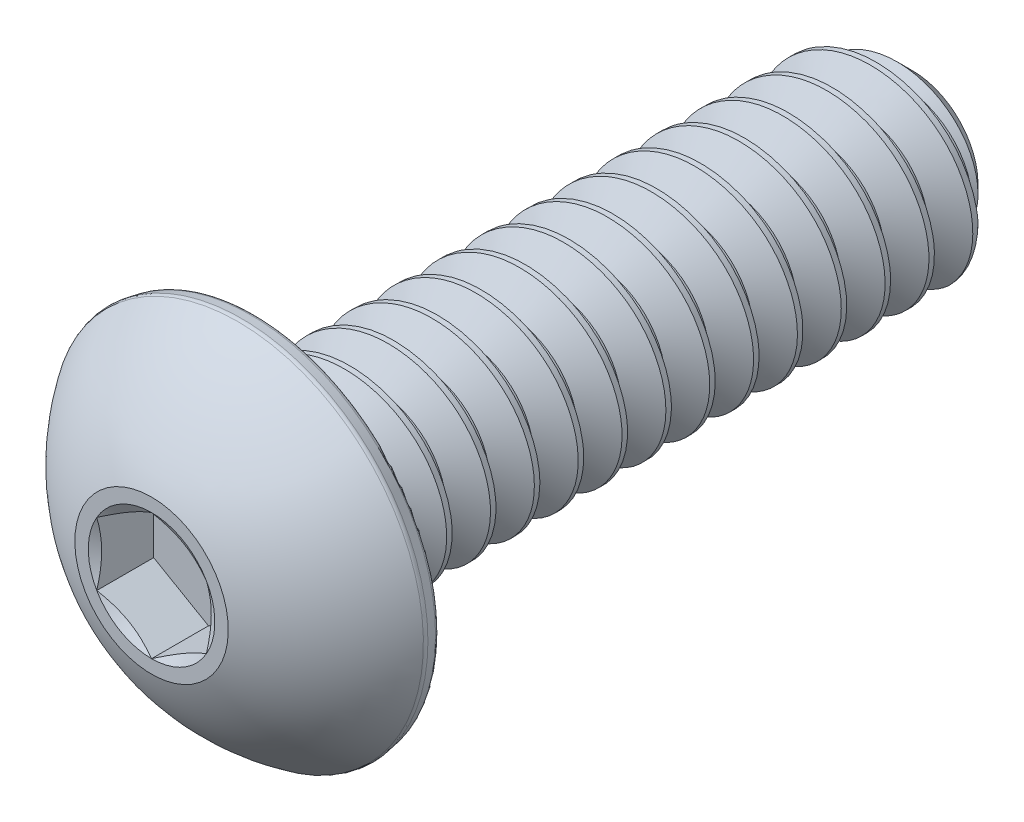
SolidWorks part; units mm, degrees
material "Stainless Steel (ferritic)"
ref_plane "Front Plane" through (0, 0, 0) normal (0, 0, 1) x (1, 0, 0)
ref_plane "Top Plane" through (0, 0, 0) normal (0, 1, 0) x (1, 0, 0)
ref_plane "Right Plane" through (0, 0, 0) normal (1, 0, 0) x (0, 0, -1)
sketch "Sketch1" plane through (0, 0, 0) normal (1, 0, 0) x (0, 0, -1)
  line L0 (-5.5118, 0) -> (5.5118, 0) construction
  line L1 (-5.5118, 0) -> (-5.5118, 2.7051)
  line L2 (-5.5118, 2.7051) -> (-4.0132, 2.7051)
  line L3 (-4.0132, 2.7051) -> (-4.0132, 1.4224)
  line L4 (-4.0132, 1.4224) -> (5.5118, 1.4224)
  line L5 (5.5118, 1.4224) -> (5.5118, 0)
  point P2 (0, 0)
  point P4 (4.8768, 0)
  point P9 (4.5593, 1.4224)
  point P10 (4.5593, -1.4224)
  point P11 (5.5118, -1.4224)
  point P15 (-4.6876, 0)
  dimension "Head Height" = 1.4986
  dimension "Head Diameter" = 5.4102
  dimension "Length" = 9.525
  dimension "Screw Size Decimal Equivalent" = 2.8448
  dimension "Thread Pitch" = 0.635
  dimension "D1" = 0.9525
  dimension "D2" = 0.8242
sketch "Sketch2" plane through (0, 0, 0) normal (0, 0, 1) x (1, 0, 0)
  line L0 (0, 1.4224) -> (0, 0) construction
  line L1 (0, 0.9165) -> (-0.7937, 0.4583)
  line L2 (-0.7937, 0.4583) -> (-0.7937, -0.4583)
  line L3 (-0.7937, -0.4583) -> (0, -0.9165)
  line L4 (0, -0.9165) -> (0.7937, -0.4583)
  line L5 (0.7937, -0.4583) -> (0.7937, 0.4583)
  line L6 (0.7937, 0.4583) -> (0, 0.9165)
  circle A0 centre (0, 0) radius 0.7937 construction
  circle A1 centre (0, 0) radius 1.1113
  point P10 (0, 1.1113)
  dimension "D1" = 2.2225
  dimension "Drive Size" = 1.5875
sketch "Sketch3" plane through (0, 0, 0) normal (1, 0, 0) x (0, 0, -1)
  line L0 (-5.5118, 0) -> (-5.5118, 1.1113)
  line L1 (-5.5118, 0) -> (-5.5118, 2.7051) construction
  line L2 (-5.5118, 2.7051) -> (-4.0132, 2.7051) construction
  line L3 (-4.238, 2.7051) -> (-4.0132, 2.6655)
  line L4 (-4.0132, 2.7051) -> (-4.0132, 1.4224) construction
  line L5 (-4.0132, 2.6655) -> (-4.0132, 1.4224)
  line L6 (-5.5118, 0) -> (5.5118, 0) construction
  line L7 (-5.5118, 0) -> (5.5118, 0)
  line L8 (5.5118, 0) -> (5.5118, 0.9462)
  line L9 (5.5118, 1.4224) -> (5.5118, 0) construction
  line L10 (5.5118, 0.9462) -> (5.0355, 1.4224)
  line L11 (-4.0132, 1.4224) -> (5.5118, 1.4224) construction
  line L12 (5.0355, 1.4224) -> (-4.0132, 1.4224)
  arc A0 (-5.5118, 1.1113) -> (-4.238, 2.7051) centre (-2.4873, 0) cw
  dimension "D1" = 0.2248
  dimension "D2" = 10
  dimension "D3" = 45
  dimension "D4" = 0.4763
revolve "Revolve1" add sketch "Sketch3" angle 360 about L7
sketch "Sketch4" plane through (0, 0, 5.5118) normal (0, 0, 1) x (1, 0, 0)
  line L0 (-0.7937, -0.4583) -> (0, -0.9165) construction
  line L1 (-0.7937, 0.4583) -> (-0.7937, -0.4583) construction
  line L2 (0, 0.9165) -> (-0.7937, 0.4583) construction
  line L3 (0.7937, 0.4583) -> (0, 0.9165) construction
  line L4 (0.7937, -0.4583) -> (0.7937, 0.4583) construction
  line L5 (0, -0.9165) -> (0.7937, -0.4583) construction
  line L6 (-0.7937, -0.4583) -> (0, -0.9165)
  line L7 (-0.7937, 0.4583) -> (-0.7937, -0.4583)
  line L8 (0, 0.9165) -> (-0.7937, 0.4583)
  line L9 (0.7937, 0.4583) -> (0, 0.9165)
  line L10 (0.7937, -0.4583) -> (0.7937, 0.4583)
  line L11 (0, -0.9165) -> (0.7937, -0.4583)
extrude "Cut-Extrude1" cut sketch "Sketch4" against normal up to vertex (0.8242 mm away) up to point (0, 0, 4.6876)
sketch "Sketch5" plane through (0, 0, 5.5118) normal (0, 0, 1) x (1, 0, 0)
  circle A0 centre (0, 0) radius 0.9165
extrude "Cut-Extrude2" cut sketch "Sketch5" against normal up to vertex (0.8242 mm away) draft 60 up to point (0, 0, 4.6876)
fillet "Fillet1" radius 0.0749 2 edges at (2.7051, 0, 4.238) (2.6655, 0, 4.0132)
split "Split1" bodies to split 106 resulting bodies 107 108 split by face at (2.6026, 0, 4.0132)
sketch "Sketch6" plane through (0, 0, -5.5118) normal (0, 0, -1) x (-1, 0, 0)
  circle A0 centre (0, 0) radius 1.4224 construction
  circle A1 centre (0, 0) radius 1.4224
curve "Helix/Spiral1" pitch 0.635 height 10.16 radius 1.4224 centre (0, 0, -5.5118) axis (0, 0, 1) start towards (0, 1, 0)
sketch "Sketch7" plane through (0, 0, 0) normal (1, 0, 0) x (0, 0, -1)
  line L0 (5.4721, 1.4911) -> (5.7896, 0.9412) construction
  line L1 (5.7896, 0.9412) -> (6.1071, 1.4911) construction
  line L2 (6.1071, 1.4911) -> (5.4721, 1.4911) construction
  line L3 (5.492, 1.4568) -> (6.0873, 1.4568)
  line L4 (6.0873, 1.4568) -> (5.8293, 1.01)
  line L5 (5.8293, 1.01) -> (5.7499, 1.01)
  line L6 (5.7499, 1.01) -> (5.492, 1.4568)
  line L7 (5.7896, 1.01) -> (5.7896, 0.9412) construction
  line L8 (5.5118, 1.4224) -> (6.0674, 1.4224) construction
  line L9 (5.7896, 1.4911) -> (5.7896, 1.4224) construction
  point P12 (5.7896, 1.4568)
  dimension "D1" = 0.635
  dimension "D2" = 0.0794
sweep "Cut-Sweep1" cut profiles "Sketch7" path "Helix/Spiral1" align with end faces yes
sketch "Sketch8" plane through (0, 0, 4.0132) normal (0, 0, -1) x (-1, 0, 0)
  circle A0 centre (0, 0) radius 1.4911
extrude "Boss-Extrude1" add sketch "Sketch8" along normal up to vertex (8.5725 mm away) draft 45 up to point (0, 1.4224, -4.5593)
equation "\"D1@Sketch1\"=\"Thread Pitch@Sketch1\"*1.5"
equation "\"D2@Sketch1\"=0.55*\"Head Height@Sketch1\""
equation "\"D1@Sketch2\"=\"Drive Size@Sketch2\"*1.4"
equation "\"D1@Sketch3\"=0.15*\"Head Height@Sketch1\""
equation "\"D4@Sketch3\"=0.75*\"Thread Pitch@Sketch1\""
equation "\"D1@Fillet1\"=.05*\"Head Height@Sketch1\""
equation "\"D4@Helix/Spiral1\"=\"Thread Pitch@Sketch1\""
equation "\"D3@Helix/Spiral1\"=\"Length@Sketch1\"+\"Thread Pitch@Sketch1\""
equation "\"D2@Sketch7\"=\"D1@Sketch7\"/8"
equation "\"D1@Sketch7\"=\"Thread Pitch@Sketch1\""
